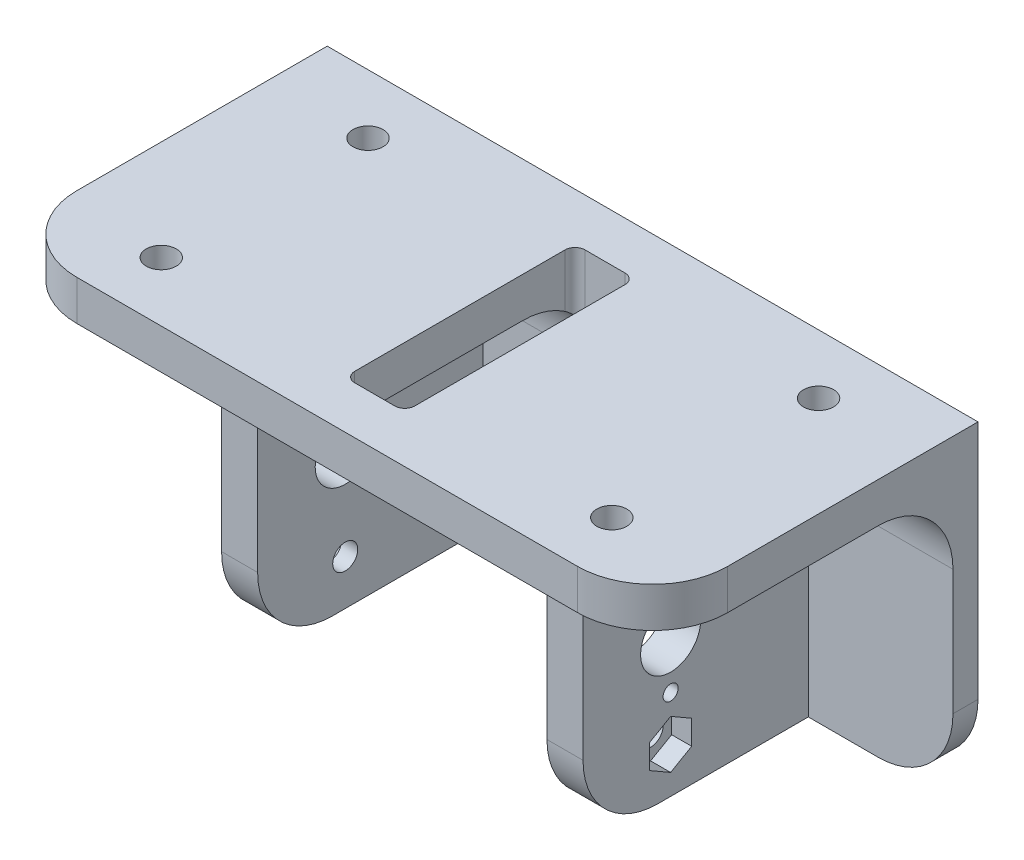
SolidWorks part; units mm, degrees
ref_plane "Front Plane" through (0, 0, 0) normal (0, 0, 1) x (1, 0, 0)
ref_plane "Top Plane" through (0, 0, 0) normal (0, 1, 0) x (1, 0, 0)
ref_plane "Right Plane" through (0, 0, 0) normal (1, 0, 0) x (0, 0, -1)
sketch "Sketch1" plane through (0, 0, 0) normal (0, 1, 0) x (1, 0, 0)
  line L0 (0, 18.2197) -> (0, -18.3609) construction
  line L1 (-19.3496, 0) -> (20.197, 0) construction
  line L2 (-45, 0) -> (-45, -10) construction
  line L3 (65, 32.5) -> (-65, 32.5)
  line L4 (-65, 32.5) -> (-65, -32.5)
  line L5 (65, -32.5) -> (-65, -32.5)
  line L6 (65, 32.5) -> (65, -32.5)
  line L7 (6, 23) -> (-6, 23)
  line L8 (-6, 23) -> (-6, -23)
  line L9 (6, -23) -> (-6, -23)
  line L10 (6, 23) -> (6, -23)
  circle A0 centre (-45, 0) radius 10 construction
  circle A6 centre (-45, 20.65) radius 3
  circle A7 centre (-45, 20.65) radius 3.4 construction
  circle A8 centre (-45, -20.65) radius 3
  circle A9 centre (-45, -20.65) radius 3.4 construction
  circle A10 centre (45, 20.65) radius 3
  circle A11 centre (45, 20.65) radius 3.4 construction
  circle A12 centre (45, 0) radius 10 construction
  circle A13 centre (45, -20.65) radius 3.4 construction
  circle A14 centre (45, -20.65) radius 3
  point P18 (-65, 0)
  point P20 (0, 32.5)
  point P21 (0, -32.5)
  point P33 (-6, 0)
  point P35 (0, -23)
  point P36 (0, 23)
  dimension "D1" = 20
  dimension "D3" = 6.8
  dimension "D4" = 41.3
  dimension "D5" = 90
  dimension "D2" = 6
  dimension "D6" = 130
  dimension "D7" = 65
  dimension "D8" = 12
  dimension "D9" = 46
extrude "Boss-Extrude1" add sketch "Sketch1" along normal blind 8
fillet "Fillet1" radius 2 4 edges at (6, 4, 23) (-6, 4, 23) (6, 4, -23) (-6, 4, -23)
sketch "Sketch2" plane through (0, 0, 0) normal (0, -1, 0) x (1, 0, 0)
  line L0 (-65, -32.5) -> (-65, -27.5)
  line L1 (-65, -32.5) -> (-65, 32.5) construction
  line L2 (-65, -27.5) -> (65, -27.5)
  line L3 (65, 32.5) -> (65, -32.5) construction
  line L4 (65, -27.5) -> (65, -32.5)
  line L5 (65, -32.5) -> (-65, -32.5)
  dimension "D1" = 5
extrude "Boss-Extrude2" add sketch "Sketch2" along normal blind 55
sketch "Sketch3" plane through (0, 0, -27.5) normal (0, 0, 1) x (1, 0, 0)
  line L0 (0, 0) -> (0, -55) construction
  line L1 (65, 0) -> (-65, 0) construction
  line L2 (65, -55) -> (-65, -55) construction
  line L3 (0, -27.5) -> (-65, -27.5) construction
  line L4 (-65, -55) -> (-65, 0) construction
  line L5 (0, -27.5) -> (65, -27.5) construction
  line L6 (65, -55) -> (65, 0) construction
  line L7 (-32.5, 0) -> (-32.5, -55) construction
  line L8 (32.5, 0) -> (32.5, -55) construction
  line L9 (-28.9, 0) -> (-36.1, 0)
  line L10 (-36.1, 0) -> (-36.1, -55)
  line L11 (-36.1, -55) -> (-28.9, -55)
  line L12 (-28.9, 0) -> (-28.9, -55)
  line L13 (28.9, 0) -> (28.9, -55)
  line L14 (36.1, -55) -> (28.9, -55)
  line L15 (36.1, 0) -> (36.1, -55)
  line L16 (28.9, 0) -> (36.1, 0)
  point P15 (-32.5, -27.5)
  point P18 (32.5, -27.5)
  dimension "D1" = 7.2
extrude "Boss-Extrude3" add sketch "Sketch3" along normal blind 45
sketch "Sketch4" plane through (-36.1, 0, 0) normal (-1, 0, 0) x (0, 0, 1)
  line L0 (0, 0) -> (0, -55) construction
  line L1 (17.5, -55) -> (-27.5, -55) construction
  line L2 (-27.5, -27.5) -> (17.5, -27.5) construction
  line L3 (-27.5, 0) -> (-27.5, -55) construction
  line L4 (17.5, 0) -> (17.5, -55) construction
  circle A0 centre (0, -27.5) radius 6
  circle A1 centre (0, -27.5) radius 18.5 construction
  circle A2 centre (0, -9) radius 2.5
  circle A3 centre (0, -46) radius 2.5
  dimension "D1" = 12
  dimension "D2" = 37
  dimension "5" = 5
extrude "Cut-Extrude1" cut sketch "Sketch4" against normal through all both and the other way through all
sketch "Sketch5" plane through (-36.1, 0, 0) normal (-1, 0, 0) x (0, 0, 1)
  line L0 (-27.5, 0) -> (-27.5, -55) construction
  line L1 (4.2, -6.5751) -> (0, -4.1503)
  line L2 (0, -4.1503) -> (-4.2, -6.5751)
  line L3 (-4.2, -6.5751) -> (-4.2, -11.4249)
  line L4 (-4.2, -11.4249) -> (0, -13.8497)
  line L5 (0, -13.8497) -> (4.2, -11.4249)
  line L6 (4.2, -11.4249) -> (4.2, -6.5751)
  line L7 (4.2, -43.5751) -> (0, -41.1503)
  line L8 (0, -41.1503) -> (-4.2, -43.5751)
  line L9 (-4.2, -43.5751) -> (-4.2, -48.4249)
  line L10 (-4.2, -48.4249) -> (0, -50.8497)
  line L11 (0, -50.8497) -> (4.2, -48.4249)
  line L12 (4.2, -48.4249) -> (4.2, -43.5751)
  line L13 (-27.5, -55) -> (-27.5, 0) construction
  circle A0 centre (0, -9) radius 4.2 construction
  circle A1 centre (0, -46) radius 4.2 construction
  point P10 (2.1, -49.6373)
  dimension "D1" = 8.4
  dimension "D2" = 8.4
extrude "Cut-Extrude2" cut sketch "Sketch5" against normal blind 4
sketch "Sketch6" plane through (36.1, 0, 0) normal (1, 0, 0) x (0, 0, -1)
  line L0 (27.5, -55) -> (27.5, 0) construction
  line L1 (4.2, -11.4249) -> (4.2, -6.5751)
  line L2 (4.2, -6.5751) -> (0, -4.1503)
  line L3 (0, -4.1503) -> (-4.2, -6.5751)
  line L4 (-4.2, -6.5751) -> (-4.2, -11.4249)
  line L5 (-4.2, -11.4249) -> (0, -13.8497)
  line L6 (0, -13.8497) -> (4.2, -11.4249)
  line L7 (-4.2, -43.5751) -> (-4.2, -48.4249)
  line L8 (-4.2, -48.4249) -> (0, -50.8497)
  line L9 (0, -50.8497) -> (4.2, -48.4249)
  line L10 (4.2, -48.4249) -> (4.2, -43.5751)
  line L11 (4.2, -43.5751) -> (0, -41.1503)
  line L12 (0, -41.1503) -> (-4.2, -43.5751)
  circle A0 centre (0, -9) radius 4.2 construction
  circle A1 centre (0, -46) radius 4.2 construction
  dimension "D1" = 8.4
  dimension "D2" = 8.4
extrude "Cut-Extrude3" cut sketch "Sketch6" against normal blind 4
sketch "Sketch7" plane through (0, 0, 0) normal (0, -1, 0) x (1, 0, 0)
  line L0 (36.1, 17.5) -> (36.1, -27.5) construction
  line L1 (50.2, -17.6478) -> (45, -14.6456)
  line L2 (45, -14.6456) -> (39.8, -17.6478)
  line L3 (39.8, -17.6478) -> (39.8, -23.6522)
  line L4 (39.8, -23.6522) -> (45, -26.6544)
  line L5 (45, -26.6544) -> (50.2, -23.6522)
  line L6 (50.2, -23.6522) -> (50.2, -17.6478)
  line L7 (50.2, 23.6522) -> (45, 26.6544)
  line L8 (45, 26.6544) -> (39.8, 23.6522)
  line L9 (39.8, 23.6522) -> (39.8, 17.6478)
  line L10 (39.8, 17.6478) -> (45, 14.6456)
  line L11 (45, 14.6456) -> (50.2, 17.6478)
  line L12 (50.2, 17.6478) -> (50.2, 23.6522)
  line L13 (0, 0) -> (0, 40) construction
  line L14 (-50.2, -23.6522) -> (-50.2, -17.6478)
  line L15 (-45, -26.6544) -> (-50.2, -23.6522)
  line L16 (-39.8, -23.6522) -> (-45, -26.6544)
  line L17 (-39.8, -17.6478) -> (-39.8, -23.6522)
  line L18 (-45, -14.6456) -> (-39.8, -17.6478)
  line L19 (-50.2, -17.6478) -> (-45, -14.6456)
  line L20 (-50.2, 17.6478) -> (-50.2, 23.6522)
  line L21 (-45, 14.6456) -> (-50.2, 17.6478)
  line L22 (-39.8, 17.6478) -> (-45, 14.6456)
  line L23 (-39.8, 23.6522) -> (-39.8, 17.6478)
  line L24 (-45, 26.6544) -> (-39.8, 23.6522)
  line L25 (-50.2, 23.6522) -> (-45, 26.6544)
  circle A0 centre (45, -20.65) radius 5.2 construction
  circle A1 centre (45, 20.65) radius 5.2 construction
  circle A3 centre (-45, -20.65) radius 5.2 construction
  circle A4 centre (-45, 20.65) radius 5.2 construction
  dimension "D1" = 10.4
  dimension "D2" = 10.4
extrude "Cut-Extrude4" cut sketch "Sketch7" against normal blind 2
sketch "Sketch8" plane through (36.1, 0, 0) normal (1, 0, 0) x (0, 0, -1)
  circle A0 centre (0, -27.5) radius 9.515 construction
  circle A1 centre (0, -17.985) radius 1.5
  circle A2 centre (0, -37.015) radius 1.5
  dimension "D1" = 19.03
  dimension "D2" = 3
extrude "Cut-Extrude5" cut sketch "Sketch8" against normal up to surface (7.2 mm away) up to face at (28.9, -43.5, 0)
sketch "Sketch9" plane through (28.9, 0, 0) normal (-1, 0, 0) x (0, 0, 1)
  line L0 (-27.5, 0) -> (-27.5, -55) construction
  line L1 (3, -38.7471) -> (3, -35.2829)
  line L2 (3, -35.2829) -> (0, -33.5509)
  line L3 (0, -33.5509) -> (-3, -35.2829)
  line L4 (-3, -35.2829) -> (-3, -38.7471)
  line L5 (-3, -38.7471) -> (0, -40.4791)
  line L6 (0, -40.4791) -> (3, -38.7471)
  line L7 (3, -19.7171) -> (3, -16.2529)
  line L8 (3, -16.2529) -> (0, -14.5209)
  line L9 (0, -14.5209) -> (-3, -16.2529)
  line L10 (-3, -16.2529) -> (-3, -19.7171)
  line L11 (-3, -19.7171) -> (0, -21.4491)
  line L12 (0, -21.4491) -> (3, -19.7171)
  circle A0 centre (0, -37.015) radius 3 construction
  circle A1 centre (0, -17.985) radius 3 construction
  dimension "D1" = 6
  dimension "D2" = 6
extrude "Cut-Extrude6" cut sketch "Sketch9" against normal blind 3.5
fillet "Fillet2" radius 15 9 edges at (-32.5, -55, 17.5) (65, 4, 32.5) (-65, 4, 32.5) (-50.55, 0, -27.5) (65, -55, -30) (-65, -55, -30) (50.55, 0, -27.5) (0, 0, -27.5) (32.5, -55, 17.5)
chamfer "Chamfer2" [suppressed] distance 1 angle 45
fillet "Fillet3" [suppressed] radius 2
